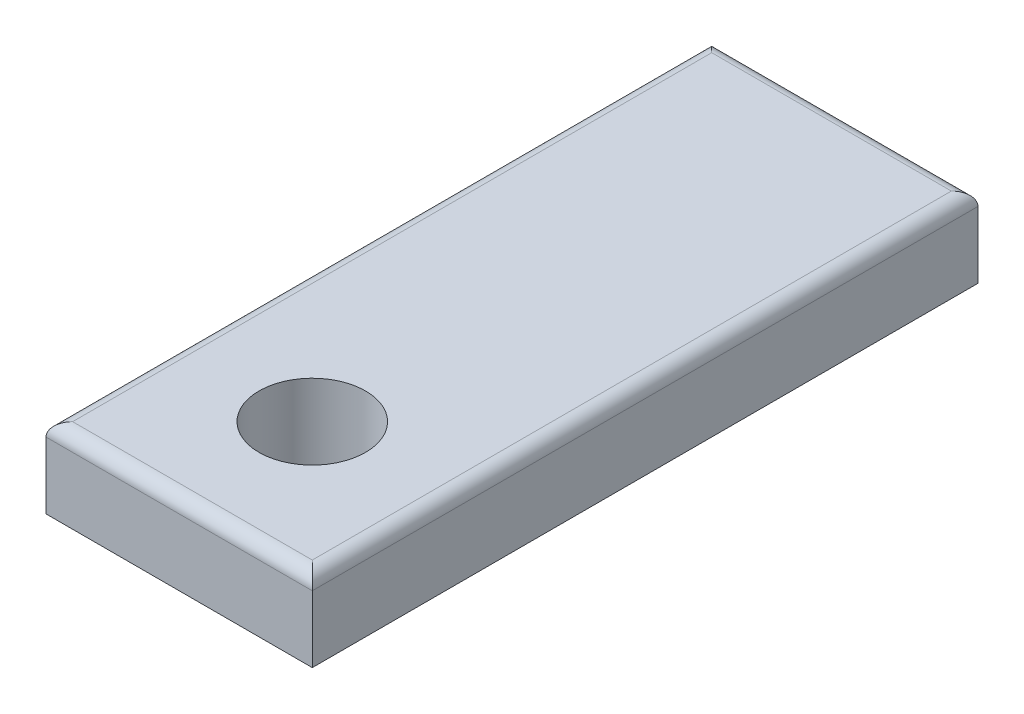
SolidWorks part; units mm, degrees
ref_plane "Front Plane" through (0, 0, 0) normal (0, 0, 1) x (1, 0, 0)
ref_plane "Top Plane" through (0, 0, 0) normal (0, 1, 0) x (1, 0, 0)
ref_plane "Right Plane" through (0, 0, 0) normal (1, 0, 0) x (0, 0, -1)
sketch "Sketch1" plane through (0, 0, 0) normal (0, 1, 0) x (1, 0, 0)
  line L1 (-5, -12.5) -> (5, -12.5)
  line L2 (-5, -12.5) -> (-5, 12.5)
  line L3 (-5, 12.5) -> (5, 12.5)
  line L4 (5, -12.5) -> (5, 12.5)
  line L5 (-5, -12.5) -> (5, 12.5) construction
  line L6 (-5, 12.5) -> (5, -12.5) construction
  point P0 (0, 0)
extrude "Boss-Extrude1" add sketch "Sketch1" along normal blind 3
sketch "Sketch2" plane through (0, 3, 0) normal (0, 1, 0) x (1, 0, 0)
  line L0 (-5, -12.5) -> (5, -12.5) construction
  circle A0 centre (0, -7.5) radius 2
  dimension "D1" = 5
extrude "Cut-Extrude1" cut sketch "Sketch2" against normal blind 3
sketch "Sketch3" plane through (0, 0, -12.5) normal (0, 0, -1) x (-1, 0, 0)
  line L0 (-5, 1.5) -> (5, 1.5)
  line L1 (-5, 3) -> (-5, 0) construction
  line L2 (5, 3) -> (5, 0) construction
fillet "Fillet1" radius 0.5 4 edges at (0, 3, 12.5) (-5, 3, 0) (0, 3, -12.5) (5, 3, 0)
